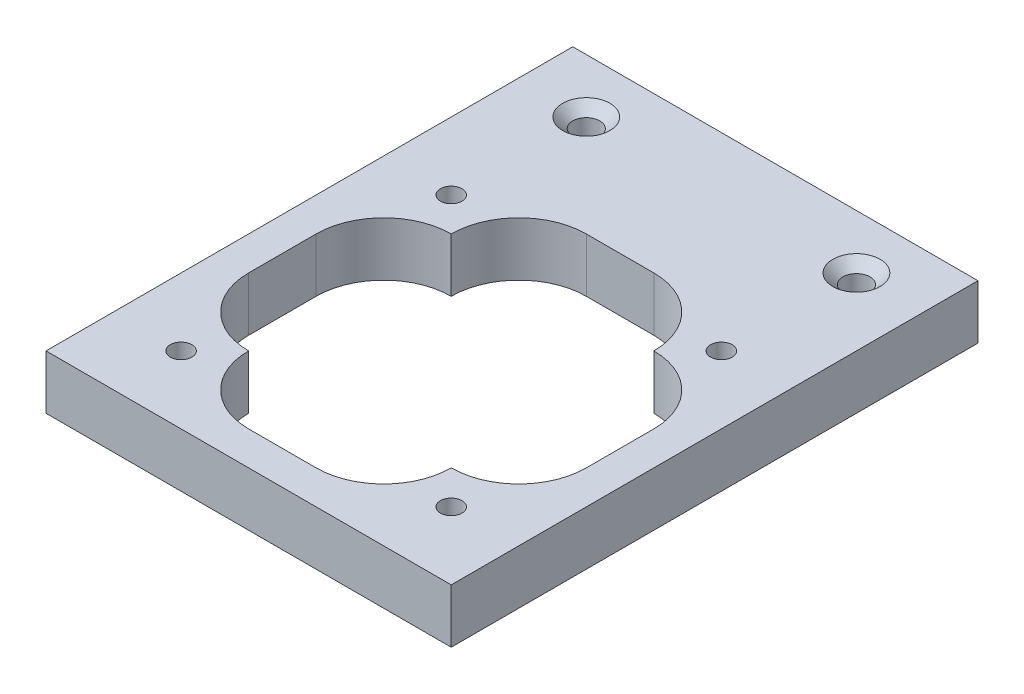
SolidWorks part; units mm, degrees
material "3.1325 (EN-AW 2017A)"
ref_plane "Ebene vorne" through (0, 0, 0) normal (0, 0, 1) x (1, 0, 0)
ref_plane "Ebene oben" through (0, 0, 0) normal (0, 1, 0) x (1, 0, 0)
ref_plane "Ebene rechts" through (0, 0, 0) normal (1, 0, 0) x (0, 0, -1)
sketch "Skizze1" plane through (0, 0, 0) normal (0, 1, 0) x (1, 0, 0)
  line L0 (0, 15) -> (0, -15) construction
  line L1 (-15, 15) -> (15, 15) construction
  line L2 (-15, 15) -> (-15, -15)
  line L3 (-15, -15) -> (15, -15)
  line L4 (15, 15) -> (15, -15)
  line L5 (-10, 0) -> (10, 0) construction
  line L6 (-10, 10) -> (10, 10) construction
  line L7 (-10, 10) -> (-10, -10) construction
  line L8 (-10, -10) -> (10, -10) construction
  line L9 (10, 10) -> (10, -10) construction
  line L10 (-15, 15) -> (-15, 24)
  line L11 (-15, 24) -> (15, 24)
  line L12 (15, 24) -> (15, 15)
  line L13 (-10, 20) -> (10, 20) construction
  line L14 (0, 20) -> (0, 15) construction
  line L15 (0, 20) -> (0, 24) construction
  line L16 (-12.5, 7.5) -> (-7.5, 7.5)
  line L17 (-7.5, 7.5) -> (-7.5, 12.5)
  line L18 (-7.5, 12.5) -> (7.5, 12.5)
  line L19 (7.5, 12.5) -> (7.5, 7.5)
  line L20 (7.5, 7.5) -> (12.5, 7.5)
  line L21 (12.5, 7.5) -> (12.5, -7.5)
  line L22 (12.5, -7.5) -> (7.5, -7.5)
  line L23 (7.5, -7.5) -> (7.5, -12.5)
  line L24 (7.5, -12.5) -> (-7.5, -12.5)
  line L25 (-7.5, -12.5) -> (-7.5, -7.5)
  line L26 (-7.5, -7.5) -> (-12.5, -7.5)
  line L27 (-12.5, -7.5) -> (-12.5, 7.5)
  line L28 (-7.5, 7.5) -> (7.5, -7.5) construction
  dimension "D1" = 20
  dimension "D2" = 30
  dimension "D3" = 9
  dimension "D4" = 4
  dimension "D5" = 5
  dimension "D6" = 15
extrude "Aufsatz-Linear austragen1" add sketch "Skizze1" along normal blind 4
fillet "Verrundung1" radius 5 8 edges at (-7.5, 2, 12.5) (-12.5, 2, 7.5) (12.5, 2, 7.5) (7.5, 2, 12.5) (12.5, 2, -7.5) (7.5, 2, -12.5) (-7.5, 2, -12.5) (-12.5, 2, -7.5)
hole_wizard "Formsenkung für M3 Senkschraube mit Innensechskant1" positions "Skizze3" profile "Skizze4" countersink size "M3" standard "DIN" end condition through all
sketch "Skizze3" plane through (0, 4, 0) normal (0, 1, 0) x (1, 0, 0)
  point P0 (-10, 20)
  point P9 (10, 20)
sketch "Skizze4" plane through (-10, 4, -20) normal (1, 0, 0) x (0, 0, 1)
  line L0 (0, 0) -> (0, 4)
  line L1 (0, 4) -> (1, 4)
  line L2 (1, 4) -> (1, 0.75)
  line L3 (1, 0.75) -> (1.75, 0)
  line L5 (1.75, 0) -> (0, 0)
  line L6 (-1, 0.75) -> (-1.75, 0) construction
  line L11 (0, -6.35) -> (0, 107.95) construction
  dimension "Bohrerdurchmesser" = 2
  dimension "Bohrungstiefe" = 4
  dimension "Senkdurchmesser (Oben)" = 3.5
  dimension "Senkwinkel (Oben)" = 90
hole_wizard "M2 Gewindebohrung1" positions "Skizze6" profile "Skizze5" tap size "M2" standard "DIN" end condition through all
sketch "Skizze6" plane through (0, 4, 0) normal (0, 1, 0) x (1, 0, 0)
  point P0 (-10, 10)
  point P3 (10, 10)
  point P6 (10, -10)
  point P9 (-10, -10)
cosmetic thread "Bohrungsgewinde1" parameters "D2"=2
cosmetic thread "Bohrungsgewinde2" parameters "D2"=2
cosmetic thread "Bohrungsgewinde3" parameters "D2"=2
cosmetic thread "Bohrungsgewinde4" parameters "D2"=2
sketch "Skizze5" plane through (-10, 4, -10) normal (1, 0, 0) x (0, 0, 1)
  line L0 (0, 0) -> (0, 4)
  line L1 (0, 4) -> (0.8, 4)
  line L2 (0.8, 4) -> (0.8, 0)
  line L5 (0.8, 0) -> (0, 0)
  line L11 (0, -6.35) -> (0, 107.95) construction
  dimension "Bohrerdurchmesser" = 1.6
  dimension "Bohrungstiefe" = 4
